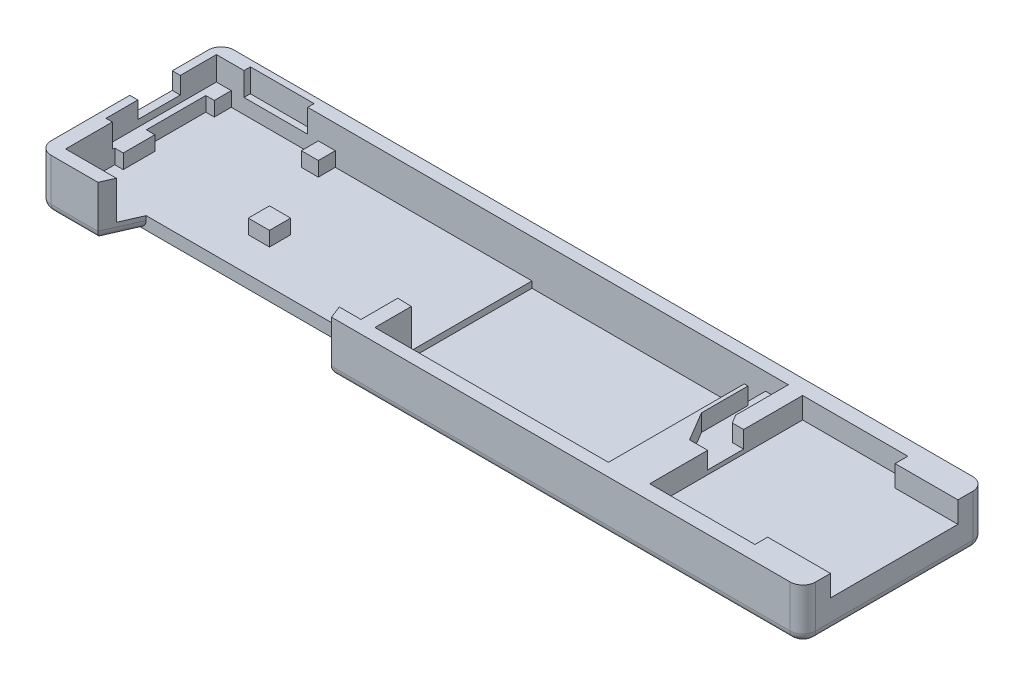
SolidWorks part; units mm, degrees
ref_plane "前视基准面" through (0, 0, 0) normal (0, 0, 1) x (1, 0, 0)
ref_plane "上视基准面" through (0, 0, 0) normal (0, 1, 0) x (1, 0, 0)
ref_plane "右视基准面" through (0, 0, 0) normal (1, 0, 0) x (0, 0, -1)
sketch "草图3" plane through (0, 0, 0) normal (0, 1, 0) x (1, 0, 0)
  line L1 (-39.9314, 29.2531) -> (140.0686, 29.2531)
  line L2 (-39.9314, 29.2531) -> (-39.9314, -13.7469)
  line L3 (-39.9314, -13.7469) -> (140.0686, -13.7469)
  line L4 (140.0686, 29.2531) -> (140.0686, -13.7469)
extrude "凸台-拉伸1" add sketch "草图3" along normal blind 12
sketch "草图4" plane through (0, 0, 0) normal (0, 1, 0) x (1, 0, 0)
  line L0 (-22.4696, -5.8589) -> (26.0023, -5.8589)
  line L1 (-39.9314, -13.7469) -> (140.0686, -13.7469) construction
  line L2 (-25.9314, -13.7469) -> (29.0686, -13.7469)
  line L5 (-25.9314, -13.7469) -> (-22.4696, -5.8589)
  line L6 (29.0686, -13.7469) -> (26.0023, -5.8589)
  point P11 (-22.4696, -5.8589)
  point P12 (26.0023, -5.8589)
extrude "切除-拉伸1" cut sketch "草图4" along normal blind 52
sketch "草图5" plane through (0, 12, 0) normal (0, 1, 0) x (1, 0, 0)
  line L6 (140.0686, -13.7469) -> (140.0686, 29.2531) construction
  line L7 (140.0686, 7.7531) -> (140.0686, 22.7531)
  line L8 (140.0686, 7.7531) -> (140.0686, -7.2469)
  line L9 (140.0686, 22.7531) -> (125.2765, 22.7531)
  line L10 (125.2765, 22.7531) -> (125.2765, -7.2469)
  line L11 (125.2765, -7.2469) -> (140.0686, -7.2469)
  point P0 (140.0686, 7.7531)
extrude "切除-拉伸2" cut sketch "草图5" against normal blind 5
sketch "草图7" plane through (0, 12, 0) normal (0, 1, 0) x (1, 0, 0)
  line L0 (125.2765, 22.7531) -> (125.2765, -7.2469) construction
  line L1 (125.2765, 7.7531) -> (125.2765, 25.7531)
  line L2 (125.2765, 7.7531) -> (125.2765, -10.2469)
  line L3 (125.2765, -10.2469) -> (100.5008, -10.2469)
  line L4 (100.5008, -10.2469) -> (100.5008, 25.7531)
  line L5 (100.5008, 25.7531) -> (125.2765, 25.7531)
  point P0 (125.2765, 7.7531)
extrude "切除-拉伸3" cut sketch "草图7" against normal blind 5
sketch "草图8" plane through (0, 12, 0) normal (0, 1, 0) x (1, 0, 0)
  line L1 (36.2763, 26.2531) -> (91.2763, 26.2531)
  line L2 (36.2763, 26.2531) -> (36.2763, -10.7469)
  line L3 (36.2763, -10.7469) -> (91.2763, -10.7469)
  line L4 (91.2763, 26.2531) -> (91.2763, -10.7469)
  line L6 (140.0686, 29.2531) -> (-39.9314, 29.2531) construction
  line L7 (29.0686, -13.7469) -> (140.0686, -13.7469) construction
  dimension "D1" = 3
  dimension "D2" = 3
extrude "切除-拉伸4" cut sketch "草图8" against normal blind 10.5
sketch "草图9" plane through (0, 12, 0) normal (0, 1, 0) x (1, 0, 0)
  line L0 (91.2763, -10.7469) -> (91.2763, 26.2531) construction
  line L1 (91.2763, 26.2531) -> (96.6358, 26.2531)
  line L2 (91.2763, 26.2531) -> (91.2763, 21.2551)
  line L4 (96.6358, 26.2531) -> (96.6358, 22.1306)
  line L5 (100.5008, 25.7531) -> (100.5008, -10.2469) construction
  line L7 (92.1327, 21.2551) -> (92.1327, 10.3104)
  line L12 (96.2367, 3.394) -> (100.5008, 3.394)
  line L13 (100.5008, 11.8772) -> (100.5008, 3.394)
  line L14 (92.1327, 10.3104) -> (96.2367, 3.394)
  line L15 (96.6358, 13.8621) -> (97.8136, 11.8772)
  line L17 (97.8136, 11.8772) -> (100.5008, 11.8772)
  line L19 (96.6358, 13.8621) -> (96.6358, 22.1306)
  line L20 (92.1327, 21.2551) -> (91.2763, 21.2551)
extrude "切除-拉伸5" cut sketch "草图9" against normal blind 4
sketch "草图10" plane through (0, 12, 0) normal (0, 1, 0) x (1, 0, 0)
  line L4 (-29.1302, -10.7469) -> (32.9986, -10.7469)
  line L5 (-29.1302, -10.7469) -> (-29.1302, -2.0631)
  line L6 (-29.1302, -2.0631) -> (32.9986, -2.0631)
  line L7 (32.9986, -10.7469) -> (32.9986, -2.0631)
extrude "切除-拉伸6" cut sketch "草图10" against normal blind 8
sketch "草图11" plane through (0, 12, 0) normal (0, 1, 0) x (1, 0, 0)
  line L0 (32.9986, -10.7469) -> (-36.5397, -10.7469)
  line L1 (36.2763, 26.2531) -> (36.2763, -10.7469) construction
  line L5 (-36.5397, 26.2531) -> (-36.5397, -10.7469)
  line L9 (36.2763, 26.2531) -> (36.2763, -2.1672)
  line L10 (-36.5397, 26.2531) -> (36.2763, 26.2531)
  line L11 (32.9986, -10.7469) -> (32.9986, -2.0631)
  line L12 (32.9986, -10.7469) -> (32.9986, -2.0631) construction
  line L13 (32.9986, -2.0631) -> (36.2763, -2.1672)
extrude "切除-拉伸8" cut sketch "草图11" against normal blind 9
fillet "圆角2" radius 2 7 edges at (140.0686, 0, -7.7531) (84.5686, 0, 13.7469) (27.5354, 0, 9.8029) (-24.2005, 0, 9.8029) (-32.9314, 0, 13.7469) (-39.9314, 0, -7.7531) (50.0686, 0, -29.2531)
fillet "圆角3" radius 3 8 edges at (-39.3456, 0.5858, -28.6673) (-39.3456, 0.5858, 13.1611) (139.4828, 0.5858, 13.1611) (139.4828, 0.5858, -28.6673) (140.0686, 7, -29.2531) (140.0686, 7, 13.7469) (-39.9314, 7, 13.7469) (-39.9314, 7, -29.2531)
sketch "草图12" plane through (-36.5397, 0, 0) normal (1, 0, 0) x (0, 0, -1)
  line L5 (7.7531, 12) -> (17.7531, 12)
  line L6 (7.7531, 12) -> (7.7531, 8)
  line L7 (7.7531, 8) -> (17.7531, 8)
  line L8 (17.7531, 12) -> (17.7531, 8)
  line L9 (26.2531, 3) -> (26.2531, 12) construction
  dimension "D1" = 10
  dimension "D2" = 8.5
  dimension "D3" = 4
extrude "切除-拉伸9" cut sketch "草图12" against normal blind 10
sketch "草图13" plane through (0, 3, 0) normal (0, 1, 0) x (1, 0, 0)
  line L0 (-36.5397, 26.2531) -> (-36.5397, -10.7469) construction
  line L1 (-36.5397, 22.2531) -> (-34.5397, 22.2531)
  line L2 (-36.5397, 22.2531) -> (-36.5397, 26.2531)
  line L3 (-36.5397, 26.2531) -> (-34.5397, 26.2531)
  line L4 (-34.5397, 22.2531) -> (-34.5397, 26.2531)
  line L5 (36.2763, 26.2531) -> (-36.5397, 26.2531) construction
  line L7 (-36.5397, 8.2531) -> (-34.5397, 8.2531)
  line L8 (-36.5397, 8.2531) -> (-36.5397, 0.8178)
  line L9 (-36.5397, 0.8178) -> (-34.5397, 0.8178)
  line L10 (-34.5397, 8.2531) -> (-34.5397, 0.8178)
  line L11 (-14.0397, 26.2531) -> (-10.0397, 26.2531)
  line L12 (-14.0397, 26.2531) -> (-14.0397, 22.2531)
  line L13 (-14.0397, 22.2531) -> (-10.0397, 22.2531)
  line L14 (-10.0397, 26.2531) -> (-10.0397, 22.2531)
  line L15 (-36.5397, 7.7531) -> (-36.5397, -10.7469) construction
  line L16 (-6.5397, 7.2531) -> (-1.5397, 7.2531)
  line L17 (-6.5397, 7.2531) -> (-6.5397, 2.2531)
  line L18 (-6.5397, 2.2531) -> (-1.5397, 2.2531)
  line L19 (-1.5397, 7.2531) -> (-1.5397, 2.2531)
  line L20 (96.6358, 26.2531) -> (-36.5397, 26.2531) construction
  point P16 (-14.0397, 24.2531)
  dimension "D1" = 14
  dimension "D2" = 4
  dimension "D3" = 2
  dimension "D4" = 2
  dimension "D5" = 22.5
  dimension "D6" = 4
  dimension "D7" = 4
  dimension "D8" = 30
  dimension "D9" = 5
  dimension "D10" = 5
  dimension "D11" = 19
extrude "凸台-拉伸2" add sketch "草图13" along normal blind 3.4
sketch "草图14" plane through (0, 12, 0) normal (0, 1, 0) x (1, 0, 0)
  line L0 (96.6358, 26.2531) -> (-36.5397, 26.2531) construction
  line L1 (-16.5397, 26.2531) -> (-31.5397, 26.2531)
  line L2 (-16.5397, 26.2531) -> (-16.5397, 27.7531)
  line L3 (-16.5397, 27.7531) -> (-31.5397, 27.7531)
  line L4 (-31.5397, 26.2531) -> (-31.5397, 27.7531)
  line L5 (91.2763, 26.2531) -> (36.2763, 26.2531) construction
  line L6 (-36.5397, 26.2531) -> (-36.5397, 17.7531) construction
  point P8 (-31.5397, 27.0031)
  dimension "D1" = 15
  dimension "D2" = 5
  dimension "D3" = 1.5
extrude "切除-拉伸10" cut sketch "草图14" against normal blind 5.5
sketch "草图15" plane through (0, 12, 0) normal (0, 1, 0) x (1, 0, 0)
  line L6 (-36.5397, 0.2531) -> (-38.0397, 0.2531)
  line L7 (-36.5397, 0.2531) -> (-36.5397, 26.2531)
  line L8 (-36.5397, 26.2531) -> (-38.0397, 26.2531)
  line L9 (-38.0397, 0.2531) -> (-38.0397, 26.2531)
  dimension "D1" = 1.5
  dimension "D2" = 26
extrude "切除-拉伸11" cut sketch "草图15" against normal blind 5.6
equation "\"3。4.00mm\"=5"
